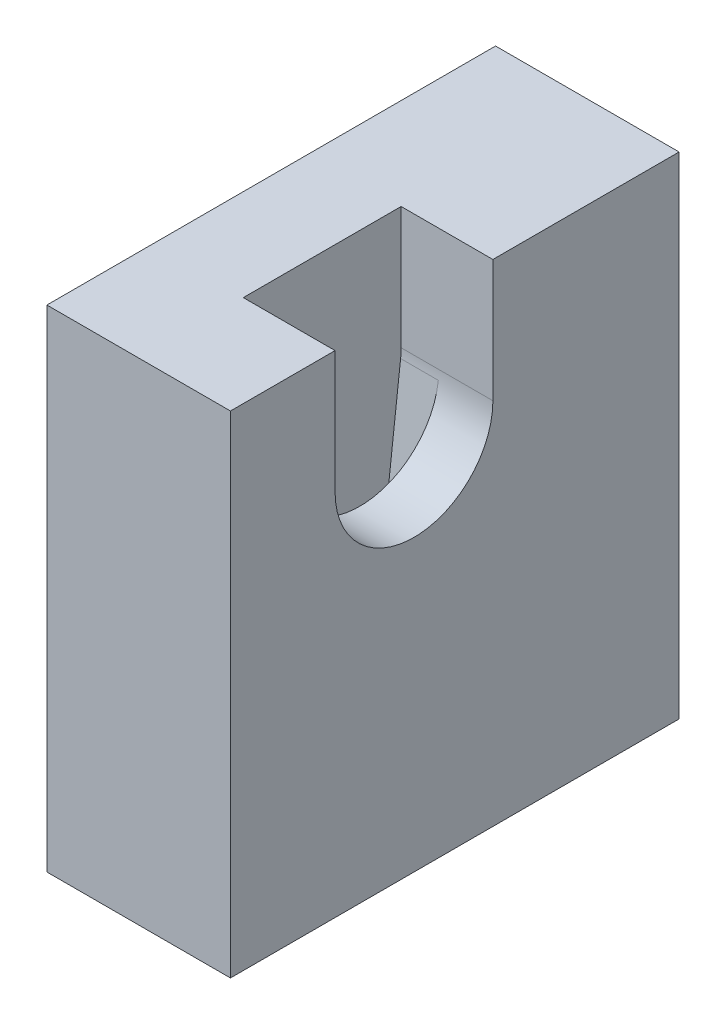
SolidWorks part; units mm, degrees
ref_plane "Front Plane" through (0, 0, 0) normal (0, 0, 1) x (1, 0, 0)
ref_plane "Top Plane" through (0, 0, 0) normal (0, 1, 0) x (1, 0, 0)
ref_plane "Right Plane" through (0, 0, 0) normal (1, 0, 0) x (0, 0, -1)
ref_axis "Axis1" through (-88.99, 0, 0) along (1, 0, 0)
sketch "Sketch1" plane through (0, 0, 0) normal (1, 0, 0) x (0, 0, -1)
  line L2 (0, 0) -> (0, 6) construction
  line L3 (9, 6) -> (-9, 6)
  line L6 (9, 6) -> (9, -18.08)
  line L7 (9, -18.08) -> (-9, -18.08)
  line L8 (-9, 6) -> (-9, -18.08)
  line L9 (0, 0) -> (9, 0) construction
  line L10 (0, -16.08) -> (0, -18.08) construction
  circle A2 centre (0, 0) radius 16.08 construction
  arc A3 (-1.9867, -14.3101) -> (1.9867, -14.3101) centre (0, -14.08) ccw construction
  point P10 (0, -16.08)
  point P11 (0, 0)
  dimension "D1" = 18
  dimension "D2" = 2
  dimension "D3" = 6
extrude "Boss-Extrude1" add sketch "Sketch1" against normal mid plane 9
sketch "Sketch2" plane through (4.5, 0, 0) normal (1, 0, 0) x (0, 0, -1)
  line L0 (9, -18.08) -> (9, 6) construction
  line L1 (9, -15.08) -> (-9, -15.08)
  line L2 (9, -15.08) -> (9, -18.08)
  line L3 (9, -18.08) -> (-9, -18.08)
  line L4 (-9, -15.08) -> (-9, -18.08)
  dimension "D1" = 3
extrude "Boss-Extrude2" [suppressed] add sketch "Sketch2" along normal up to surface (28.1955 mm away)
sketch "Sketch3" plane through (0, 0, 0) normal (1, 0, 0) x (0, 0, -1)
  line L0 (2.2351, -14.3389) -> (3.8443, -0.4453)
  line L1 (-3.8443, -0.4453) -> (-2.2351, -14.3389)
  line L2 (1.9867, -14.3101) -> (3.596, -0.4165)
  line L3 (-3.596, -0.4165) -> (-1.9867, -14.3101)
  line L4 (1.9867, -14.3101) -> (3.596, -0.4165) construction
  line L5 (-3.596, -0.4165) -> (-1.9867, -14.3101) construction
  line L6 (-3.87, 0) -> (-3.87, 6)
  line L7 (-3.87, 6) -> (3.87, 6)
  line L8 (3.87, 6) -> (3.87, 0)
  line L9 (9, 6) -> (-9, 6) construction
  arc A0 (3.8443, -0.4453) -> (3.87, 0) centre (0, 0) ccw
  arc A1 (-2.2351, -14.3389) -> (2.2351, -14.3389) centre (0, -14.08) ccw
  arc A2 (-1.9867, -14.3101) -> (1.9867, -14.3101) centre (0, -14.08) ccw
  arc A3 (3.596, -0.4165) -> (-3.596, -0.4165) centre (0, 0) ccw
  arc A4 (-1.9867, -14.3101) -> (1.9867, -14.3101) centre (0, -14.08) ccw construction
  arc A5 (3.596, -0.4165) -> (-3.596, -0.4165) centre (0, 0) ccw construction
  arc A6 (-3.87, 0) -> (-3.8443, -0.4453) centre (0, 0) ccw
  arc A7 (3.8443, -0.4453) -> (-3.8443, -0.4453) centre (0, 0) ccw construction
  dimension "D1" = 0
  dimension "D2" = 0.25
extrude "Cut-Extrude1" cut sketch "Sketch3" along normal offset from surface (1.85 mm away) 0.25 offset beyond the face yes
sketch "Sketch4" plane through (0, 0, 0) normal (1, 0, 0) x (0, 0, -1)
  line L0 (3.87, 0) -> (3.87, 6) construction
  line L1 (-3.87, 6) -> (-3.87, 0) construction
  line L2 (3.87, 0) -> (3.87, 6)
  line L3 (-3.87, 6) -> (-3.87, 0)
  line L4 (3.87, 6) -> (-3.87, 6) construction
  line L5 (3.87, 6) -> (-3.87, 6)
  circle A2 centre (0, 0) radius 3.87
  arc A3 (-3.87, 0) -> (3.87, 0) centre (0, 0) ccw
  dimension "D1" = 0.25
extrude "Cut-Extrude2" cut sketch "Sketch4" along normal up to surface (4.5 mm away) up to face at (4.5, -6.04, 0)
sketch "Sketch5" [suppressed] plane through (4, 0, 0) normal (1, 0, 0) x (0, 0, -1)
  line L1 (-7.5, -23.3871) -> (-4.5, -23.3871)
  line L2 (-7.5, -23.3871) -> (-7.5, -19.3871)
  line L3 (-7.5, -19.3871) -> (-4.5, -19.3871)
  line L4 (-4.5, -23.3871) -> (-4.5, -19.3871)
  line L5 (7.5, -23.3871) -> (4.5, -23.3871)
  line L6 (7.5, -23.3871) -> (7.5, -19.3871)
  line L7 (7.5, -19.3871) -> (4.5, -19.3871)
  line L8 (4.5, -23.3871) -> (4.5, -19.3871)
  dimension "D1" = 4
  dimension "D2" = 3
extrude "Boss-Extrude3" [suppressed] add sketch "Sketch5" along normal up to surface (28.1955 mm away) up to face at (-4.5, -6.04, 0)
sketch "Sketch6" plane through (0, -18.08, 0) normal (0, -1, 0) x (1, 0, 0)
  line L0 (4.5, 9) -> (4.5, -9) construction
  line L2 (0, 0) -> (-16.6927, 0) construction
  line L7 (-4.5, -13) -> (4.5, -13)
  line L8 (4.5, -13) -> (4.5, -9)
  line L10 (4.5, -9) -> (-4.5, -9)
  line L11 (-4.5, -9) -> (-4.5, -13)
  line L12 (-4.5, 9) -> (-4.5, -9) construction
  point P4 (0, 0)
  point P9 (-4.5, -7.5)
  dimension "D1" = 4
extrude "Boss-Extrude4" add sketch "Sketch6" against normal up to surface (24.08 mm away) up to face at (1.125, 6, 0)
hole_wizard "#8-32 Tapped Hole1" positions "Sketch7" profile "Sketch8" tap size "#8-32" standard "ANSI Inch"
sketch "Sketch7" plane through (0, -18.08, 0) normal (0, -1, 0) x (-1, 0, 0)
  line L0 (0, 13) -> (0, 9) construction
  line L3 (0, -9) -> (0, -5) construction
  line L16 (4.5, 13) -> (-4.5, 13) construction
  line L17 (4.5, -9) -> (-4.5, -9) construction
  point P0 (0, -5)
  point P2 (0, 9)
  point P99 (0, 15.2347)
  point P100 (0, 15.5)
  point P103 (0, -7.5)
  dimension "D1" = 14
sketch "Sketch8" plane through (0, -18.08, 5) normal (1, 0, 0) x (0, 0, -1)
  line L0 (0, 0) -> (0, 11.0378)
  line L1 (0, 11.0378) -> (1.7272, 10)
  line L2 (1.7272, 10) -> (1.7272, 0)
  line L5 (1.7272, 0) -> (0, 0)
  line L10 (0, 11.0378) -> (-1.7272, 10) construction
  line L11 (0, -6.35) -> (0, 107.95) construction
  dimension "Tap Drill Dia." = 3.4544
  dimension "Tap Drill Depth" = 10
  dimension "Drill Angle" = 118
cosmetic thread "Hole Thread1" parameters "D1"=8.33, "D2"=4.1656
cosmetic thread "Hole Thread5" parameters "D1"=8.33, "D2"=4.1656
